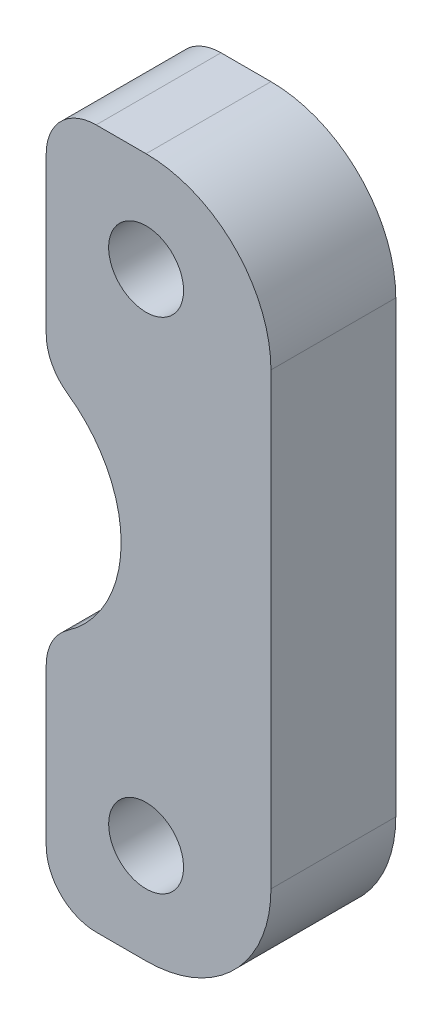
SolidWorks part; units mm, degrees
ref_plane "Plan de face" through (0, 0, 0) normal (0, 0, 1) x (1, 0, 0)
ref_plane "Plan de dessus" through (0, 0, 0) normal (0, 1, 0) x (1, 0, 0)
ref_plane "Plan de droite" through (0, 0, 0) normal (1, 0, 0) x (0, 0, -1)
sketch "Esquisse1" plane through (0, 0, 0) normal (0, 0, 1) x (1, 0, 0)
  line L0 (0, 0) -> (13.8043, 0) construction
  line L1 (0, 0) -> (0, 13.7674) construction
  line L2 (2, 19.222) -> (2, -18.3576) construction
  line L3 (2, 14) -> (2, 4.5826)
  line L4 (2, -14) -> (2, -4.5826)
  line L5 (2, 14) -> (11, 14)
  line L6 (11, 14) -> (11, -14)
  line L7 (11, -14) -> (2, -14)
  circle A0 centre (6, 10) radius 1.5
  circle A1 centre (6, -10) radius 1.5
  circle A2 centre (0, 0) radius 5 construction
  arc A3 (2, 4.5826) -> (2, -4.5826) centre (0, 0) cw
  point P15 (2, -18.3576)
  point P19 (2, 19.222)
  dimension "D1" = 3
  dimension "D4" = 10
  dimension "D2" = 20
  dimension "D3" = 6
  dimension "D5" = 2
  dimension "D6" = 5
  dimension "D7" = 4
extrude "Boss.-Extru.1" add sketch "Esquisse1" along normal blind 5
fillet "Congé1" radius 5 2 edges at (11, -14, 2.5) (11, 14, 2.5)
fillet "Congé2" radius 2 4 edges at (2, -14, 2.5) (2, -4.5826, 2.5) (2, 4.5826, 2.5) (2, 14, 2.5)
